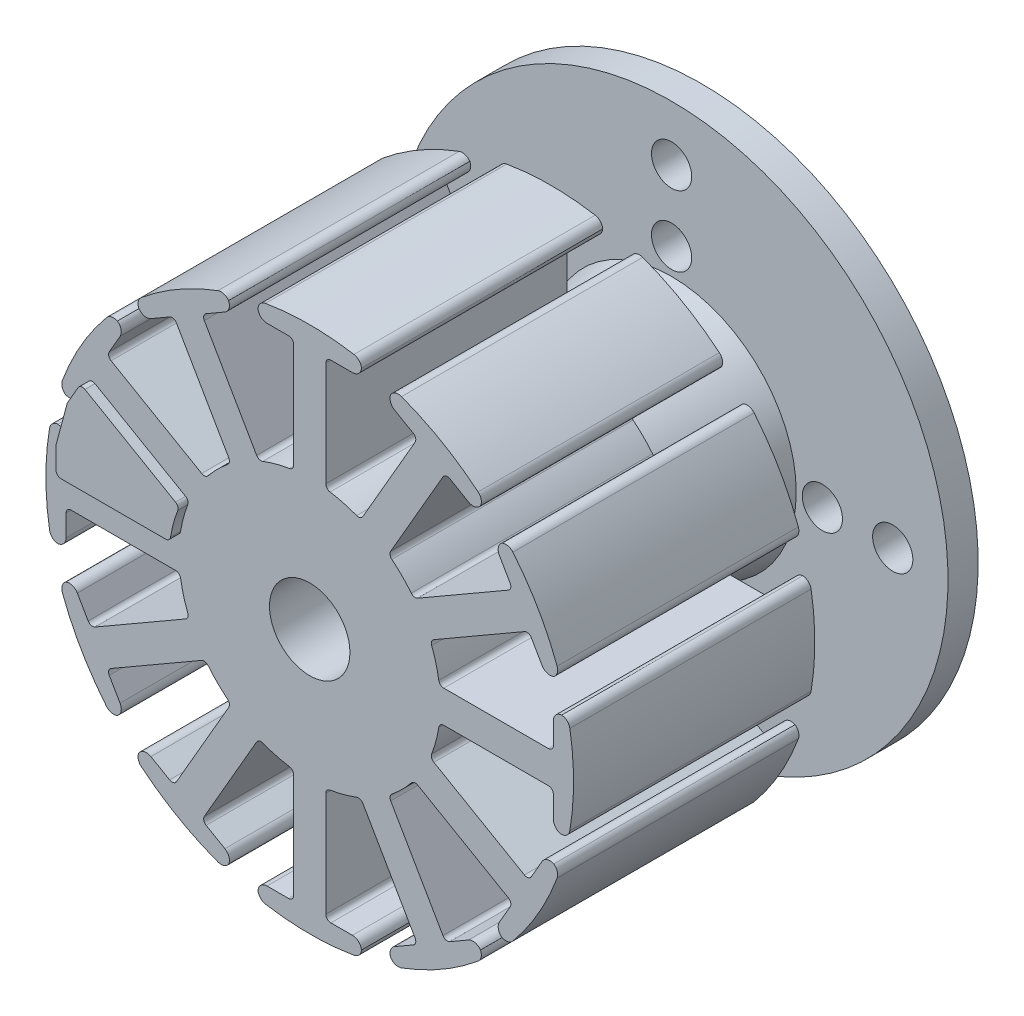
SolidWorks part; units mm, degrees
material "1023 炭素鋼板 (SS)"
ref_plane "正面" through (0, 0, 0) normal (0, 0, 1) x (1, 0, 0)
ref_plane "平面" through (0, 0, 0) normal (0, 1, 0) x (1, 0, 0)
ref_plane "右側面" through (0, 0, 0) normal (1, 0, 0) x (0, 0, -1)
sketch "ｽｹｯﾁ1" plane through (0, 0, 0) normal (0, 0, 1) x (1, 0, 0)
  line L0 (0, 26.25) -> (0, 0) construction
  line L1 (-5.15, 25.7399) -> (5.15, 25.7399) construction
  line L2 (-1.6, 24.2399) -> (-1.6, 12.9012)
  line L3 (1.6, 24.2399) -> (1.6, 12.9012)
  line L4 (13.5056, 20.1923) -> (7.8362, 10.3727)
  line L5 (16.58, 18.4173) -> (13.5056, 20.1923)
  line L6 (-5.15, 25.7399) -> (-5.15, 24.2399)
  line L7 (-5.15, 24.2399) -> (-1.6, 24.2399)
  line L8 (5.15, 25.7399) -> (5.15, 24.2399)
  line L9 (5.15, 24.2399) -> (1.6, 24.2399)
  line L10 (17.33, 19.7164) -> (16.58, 18.4173)
  line L11 (8.4099, 24.8664) -> (7.6599, 23.5673)
  line L12 (7.6599, 23.5673) -> (10.7343, 21.7923)
  line L13 (10.7343, 21.7923) -> (5.0649, 11.9727)
  line L14 (21.7923, 10.7343) -> (11.9727, 5.0649)
  line L15 (23.5673, 7.6599) -> (21.7923, 10.7343)
  line L16 (24.8664, 8.4099) -> (23.5673, 7.6599)
  line L17 (19.7164, 17.33) -> (18.4173, 16.58)
  line L18 (18.4173, 16.58) -> (20.1923, 13.5056)
  line L19 (20.1923, 13.5056) -> (10.3727, 7.8362)
  line L20 (24.2399, -1.6) -> (12.9012, -1.6)
  line L21 (24.2399, -5.15) -> (24.2399, -1.6)
  line L22 (25.7399, -5.15) -> (24.2399, -5.15)
  line L23 (25.7399, 5.15) -> (24.2399, 5.15)
  line L24 (24.2399, 5.15) -> (24.2399, 1.6)
  line L25 (24.2399, 1.6) -> (12.9012, 1.6)
  line L26 (20.1923, -13.5056) -> (10.3727, -7.8362)
  line L27 (18.4173, -16.58) -> (20.1923, -13.5056)
  line L28 (19.7164, -17.33) -> (18.4173, -16.58)
  line L29 (24.8664, -8.4099) -> (23.5673, -7.6599)
  line L30 (23.5673, -7.6599) -> (21.7923, -10.7343)
  line L31 (21.7923, -10.7343) -> (11.9727, -5.0649)
  line L32 (10.7343, -21.7923) -> (5.0649, -11.9727)
  line L33 (7.6599, -23.5673) -> (10.7343, -21.7923)
  line L34 (8.4099, -24.8664) -> (7.6599, -23.5673)
  line L35 (17.33, -19.7164) -> (16.58, -18.4173)
  line L36 (16.58, -18.4173) -> (13.5056, -20.1923)
  line L37 (13.5056, -20.1923) -> (7.8362, -10.3727)
  line L38 (-1.6, -24.2399) -> (-1.6, -12.9012)
  line L39 (-5.15, -24.2399) -> (-1.6, -24.2399)
  line L40 (-5.15, -25.7399) -> (-5.15, -24.2399)
  line L41 (5.15, -25.7399) -> (5.15, -24.2399)
  line L42 (5.15, -24.2399) -> (1.6, -24.2399)
  line L43 (1.6, -24.2399) -> (1.6, -12.9012)
  line L44 (-13.5056, -20.1923) -> (-7.8362, -10.3727)
  line L45 (-16.58, -18.4173) -> (-13.5056, -20.1923)
  line L46 (-17.33, -19.7164) -> (-16.58, -18.4173)
  line L47 (-8.4099, -24.8664) -> (-7.6599, -23.5673)
  line L48 (-7.6599, -23.5673) -> (-10.7343, -21.7923)
  line L49 (-10.7343, -21.7923) -> (-5.0649, -11.9727)
  line L50 (-21.7923, -10.7343) -> (-11.9727, -5.0649)
  line L51 (-23.5673, -7.6599) -> (-21.7923, -10.7343)
  line L52 (-24.8664, -8.4099) -> (-23.5673, -7.6599)
  line L53 (-19.7164, -17.33) -> (-18.4173, -16.58)
  line L54 (-18.4173, -16.58) -> (-20.1923, -13.5056)
  line L55 (-20.1923, -13.5056) -> (-10.3727, -7.8362)
  line L56 (-24.2399, 1.6) -> (-12.9012, 1.6)
  line L57 (-24.2399, 5.15) -> (-24.2399, 1.6)
  line L58 (-25.7399, 5.15) -> (-24.2399, 5.15)
  line L59 (-25.7399, -5.15) -> (-24.2399, -5.15)
  line L60 (-24.2399, -5.15) -> (-24.2399, -1.6)
  line L61 (-24.2399, -1.6) -> (-12.9012, -1.6)
  line L62 (-20.1923, 13.5056) -> (-10.3727, 7.8362)
  line L63 (-18.4173, 16.58) -> (-20.1923, 13.5056)
  line L64 (-19.7164, 17.33) -> (-18.4173, 16.58)
  line L65 (-24.8664, 8.4099) -> (-23.5673, 7.6599)
  line L66 (-23.5673, 7.6599) -> (-21.7923, 10.7343)
  line L67 (-21.7923, 10.7343) -> (-11.9727, 5.0649)
  line L68 (-10.7343, 21.7923) -> (-5.0649, 11.9727)
  line L69 (-7.6599, 23.5673) -> (-10.7343, 21.7923)
  line L70 (-8.4099, 24.8664) -> (-7.6599, 23.5673)
  line L71 (-17.33, 19.7164) -> (-16.58, 18.4173)
  line L72 (-16.58, 18.4173) -> (-13.5056, 20.1923)
  line L73 (-13.5056, 20.1923) -> (-7.8362, 10.3727)
  circle A0 centre (0, 0) radius 26.25 construction
  arc A1 (-1.6, 12.9012) -> (-5.0649, 11.9727) centre (0, 0) ccw
  circle A2 centre (0, 0) radius 4
  arc A3 (-5.15, 25.7399) -> (5.15, 25.7399) centre (0, 0) cw
  arc A4 (8.4099, 24.8664) -> (17.33, 19.7164) centre (0, 0) cw
  arc A5 (19.7164, 17.33) -> (24.8664, 8.4099) centre (0, 0) cw
  arc A6 (25.7399, 5.15) -> (25.7399, -5.15) centre (0, 0) cw
  arc A7 (24.8664, -8.4099) -> (19.7164, -17.33) centre (0, 0) cw
  arc A8 (17.33, -19.7164) -> (8.4099, -24.8664) centre (0, 0) cw
  arc A9 (5.15, -25.7399) -> (-5.15, -25.7399) centre (0, 0) cw
  arc A10 (-8.4099, -24.8664) -> (-17.33, -19.7164) centre (0, 0) cw
  arc A11 (-19.7164, -17.33) -> (-24.8664, -8.4099) centre (0, 0) cw
  arc A12 (-25.7399, -5.15) -> (-25.7399, 5.15) centre (0, 0) cw
  arc A13 (-24.8664, 8.4099) -> (-19.7164, 17.33) centre (0, 0) cw
  arc A14 (-17.33, 19.7164) -> (-8.4099, 24.8664) centre (0, 0) cw
  arc A15 (5.0649, 11.9727) -> (1.6, 12.9012) centre (0, 0) ccw
  arc A16 (10.3727, 7.8362) -> (7.8362, 10.3727) centre (0, 0) ccw
  arc A17 (12.9012, 1.6) -> (11.9727, 5.0649) centre (0, 0) ccw
  arc A18 (11.9727, -5.0649) -> (12.9012, -1.6) centre (0, 0) ccw
  arc A19 (7.8362, -10.3727) -> (10.3727, -7.8362) centre (0, 0) ccw
  arc A20 (1.6, -12.9012) -> (5.0649, -11.9727) centre (0, 0) ccw
  arc A21 (-5.0649, -11.9727) -> (-1.6, -12.9012) centre (0, 0) ccw
  arc A22 (-10.3727, -7.8362) -> (-7.8362, -10.3727) centre (0, 0) ccw
  arc A23 (-12.9012, -1.6) -> (-11.9727, -5.0649) centre (0, 0) ccw
  arc A24 (-11.9727, 5.0649) -> (-12.9012, 1.6) centre (0, 0) ccw
  arc A25 (-7.8362, 10.3727) -> (-10.3727, 7.8362) centre (0, 0) ccw
  point P105 (0, 0)
  dimension "D1" = 52.5
  dimension "D4" = 8
  dimension "D5" = 26
  dimension "D2" = 1.6
  dimension "D3" = 1.6
  dimension "D6" = 10.3
  dimension "D7" = 1.5
  dimension "D8" = 12
extrude "ﾎﾞｽ - 押し出し1" add sketch "ｽｹｯﾁ1" along normal blind 24
fillet "ﾌｨﾚｯﾄ1" radius 0.9 4 edges at (-16.58, 18.4173, 12) (-17.33, 19.7164, 12) (-8.4099, 24.8664, 12) (-7.6599, 23.5673, 12)
fillet "ﾌｨﾚｯﾄ2" radius 0.9 12 edges at (23.5673, 7.6599, 12) (16.58, 18.4173, 12) (18.4173, 16.58, 12) (24.8664, 8.4099, 12) (5.15, 24.2399, 12) (19.7164, 17.33, 12) (17.33, 19.7164, 12) (7.6599, 23.5673, 12) (8.4099, 24.8664, 12) (5.15, 25.7399, 12) (-5.15, 24.2399, 12) (-5.15, 25.7399, 12)
fillet "ﾌｨﾚｯﾄ3" radius 0.9 8 edges at (19.7164, -17.33, 12) (18.4173, -16.58, 12) (24.8664, -8.4099, 12) (23.5673, -7.6599, 12) (24.2399, 5.15, 12) (24.2399, -5.15, 12) (25.7399, -5.15, 12) (25.7399, 5.15, 12)
fillet "ﾌｨﾚｯﾄ4" radius 0.9 24 edges at (-19.7164, 17.33, 12) (-18.4173, 16.58, 12) (-24.8664, 8.4099, 12) (-23.5673, 7.6599, 12) (-24.2399, 5.15, 12) (-25.7399, 5.15, 12) (-24.2399, -5.15, 12) (-25.7399, -5.15, 12) (-23.5673, -7.6599, 12) (-24.8664, -8.4099, 12) (-19.7164, -17.33, 12) (-18.4173, -16.58, 12) (-16.58, -18.4173, 12) (-17.33, -19.7164, 12) (-8.4099, -24.8664, 12) (-7.6599, -23.5673, 12) (-5.15, -24.2399, 12) (-5.15, -25.7399, 12) (5.15, -24.2399, 12) (5.15, -25.7399, 12) (8.4099, -24.8664, 12) (7.6599, -23.5673, 12) (17.33, -19.7164, 12) (16.58, -18.4173, 12)
fillet "ﾌｨﾚｯﾄ5" radius 0.5 26 edges at (-21.7923, -10.7343, 12) (-11.9727, -5.0649, 12) (-20.1923, -13.5056, 12) (-10.3727, -7.8362, 12) (-13.5056, -20.1923, 12) (-7.8362, -10.3727, 12) (-10.7343, -21.7923, 12) (-5.0649, -11.9727, 12) (-1.6, -24.2399, 12) (-1.6, -12.9012, 12) (1.6, -24.2399, 12) (1.6, -12.9012, 12) (5.0649, -11.9727, 12) (10.7343, -21.7923, 12) (13.5056, -20.1923, 12) (7.8362, -10.3727, 12) (20.1923, -13.5056, 12) (10.3727, -7.8362, 12) (21.7923, -10.7343, 12) (11.9727, -5.0649, 12) (12.9012, -1.6, 12) (24.2399, -1.6, 12) (24.2399, 1.6, 12) (12.9012, 1.6, 12) (11.9727, 5.0649, 12) (21.7923, 10.7343, 12)
fillet "ﾌｨﾚｯﾄ6" radius 0.5 22 edges at (20.1923, 13.5056, 12) (10.3727, 7.8362, 12) (7.8362, 10.3727, 12) (13.5056, 20.1923, 12) (10.7343, 21.7923, 12) (5.0649, 11.9727, 12) (-1.6, 12.9012, 12) (-1.6, 24.2399, 12) (1.6, 24.2399, 12) (-10.7343, 21.7923, 12) (-7.8362, 10.3727, 12) (-20.1923, 13.5056, 12) (-13.5056, 20.1923, 12) (-21.7923, 10.7343, 12) (-11.9727, 5.0649, 12) (1.6, 12.9012, 12) (-5.0649, 11.9727, 12) (-10.3727, 7.8362, 12) (-24.2399, 1.6, 12) (-12.9012, 1.6, 12) (-24.2399, -1.6, 12) (-12.9012, -1.6, 12)
sketch "ｽｹｯﾁ5" plane through (0, 0, 0) normal (1, 0, 0) x (0, 0, -1)
  line L0 (0, 0) -> (15, 0)
  line L1 (15, 0) -> (15, 13)
  line L2 (15, 13) -> (0, 10)
  line L3 (0, 10) -> (0, 0)
  line L4 (-24, 4) -> (-24, -4) construction
  dimension "D1" = 39
  dimension "D2" = 13
  dimension "D3" = 10
revolve "回転1" add sketch "ｽｹｯﾁ5" angle 360 about L0
sketch "ｽｹｯﾁ6" plane through (0, 0, -15) normal (0, 0, -1) x (-1, 0, 0)
  circle A0 centre (0, 0) radius 27.5
  dimension "D1" = 55
extrude "ﾎﾞｽ - 押し出し3" add sketch "ｽｹｯﾁ6" against normal blind 3
sketch "ｽｹｯﾁ7" plane through (0, 0, -15) normal (0, 0, -1) x (-1, 0, 0)
  circle A0 centre (0, 0) radius 15 construction
  circle A1 centre (0, 0) radius 22 construction
  circle A2 centre (0, 22) radius 2
  circle A3 centre (0, 15) radius 2
  circle A4 centre (15, 0) radius 2
  circle A5 centre (22, 0) radius 2
  circle A6 centre (-22, 0) radius 2
  circle A7 centre (-15, 0) radius 2
  circle A8 centre (0, -15) radius 2
  circle A9 centre (0, -22) radius 2
  circle A10 centre (0, 0) radius 27.5 construction
  dimension "D1" = 30
  dimension "D2" = 4
extrude "ｶｯﾄ - 押し出し1" cut sketch "ｽｹｯﾁ7" against normal up to next
sketch "ｽｹｯﾁ8" plane through (0, 0, -15) normal (0, 0, -1) x (-1, 0, 0)
  circle A0 centre (0, 0) radius 10.6
  dimension "D1" = 21.2
extrude "ｶｯﾄ - 押し出し2" cut sketch "ｽｹｯﾁ8" against normal blind 1
sketch "ｽｹｯﾁ9" plane through (0, 0, -14) normal (0, 0, -1) x (-1, 0, 0)
  circle A0 centre (0, 0) radius 4 construction
  circle A1 centre (0, 0) radius 4
extrude "ｶｯﾄ - 押し出し3" cut sketch "ｽｹｯﾁ9" against normal through all
sketch "ｽｹｯﾁ10" plane through (0, 0, 24) normal (0, 0, 1) x (1, 0, 0)
  line L0 (-24.2399, 2.1) -> (-24.2399, 4.25) construction
  line L1 (-13.3357, 1.6) -> (-23.7399, 1.6) construction
  line L2 (-21.3593, 10.4843) -> (-12.349, 5.2822) construction
  line L3 (-23.1173, 8.4393) -> (-22.0423, 10.3013) construction
  line L4 (-24.2399, 2.1) -> (-24.2399, 4.25)
  line L5 (-13.3357, 1.6) -> (-23.7399, 1.6)
  line L6 (-21.3593, 10.4843) -> (-12.349, 5.2822)
  line L7 (-23.1173, 8.4393) -> (-22.0423, 10.3013)
  line L8 (-24.2399, 4.25) -> (-23.1173, 8.4393)
  arc A0 (-24.2399, 2.1) -> (-23.7399, 1.6) centre (-23.7399, 2.1) ccw construction
  arc A1 (-13.3357, 1.6) -> (-12.8418, 2.0222) centre (-13.3357, 2.1) ccw construction
  arc A2 (-12.1324, 4.6696) -> (-12.8418, 2.0222) centre (0, 0) ccw construction
  arc A3 (-12.1324, 4.6696) -> (-12.349, 5.2822) centre (-12.599, 4.8492) ccw construction
  arc A4 (-21.3593, 10.4843) -> (-22.0423, 10.3013) centre (-21.6093, 10.0513) ccw construction
  arc A5 (-24.2399, 2.1) -> (-23.7399, 1.6) centre (-23.7399, 2.1) ccw
  arc A6 (-13.3357, 1.6) -> (-12.8418, 2.0222) centre (-13.3357, 2.1) ccw
  arc A7 (-12.1324, 4.6696) -> (-12.8418, 2.0222) centre (0, 0) ccw
  arc A8 (-12.1324, 4.6696) -> (-12.349, 5.2822) centre (-12.599, 4.8492) ccw
  arc A9 (-21.3593, 10.4843) -> (-22.0423, 10.3013) centre (-21.6093, 10.0513) ccw
extrude "ﾎﾞｽ - 押し出し4" add sketch "ｽｹｯﾁ10" along normal blind 1 separate body
